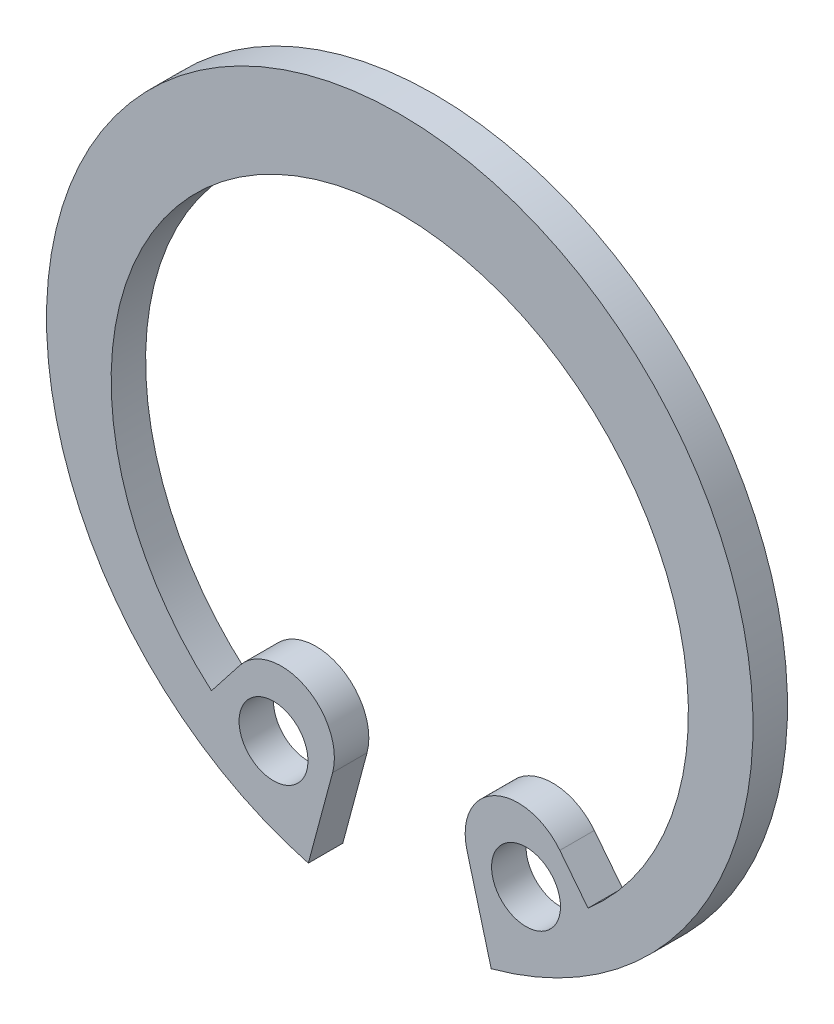
SolidWorks part; units mm, degrees
material "Steel AISI 4130 , normalized at 870°C"
ref_plane "Front" through (0, 0, 0) normal (0, 0, 1) x (1, 0, 0)
ref_plane "Top" through (0, 0, 0) normal (0, 1, 0) x (1, 0, 0)
ref_plane "Right" through (0, 0, 0) normal (1, 0, 0) x (0, 0, -1)
sketch "Layout" plane through (0, 0, 0) normal (0, 0, 1) x (1, 0, 0)
  line L0 (0, 0) -> (2.6529, -9.9007) construction
  line L1 (0, 0) -> (0, -2.175) construction
  line L2 (0, 0) -> (6.3209, -8.069) construction
  line L3 (0, 10.25) -> (0, 9) construction
  line L4 (0, -10.25) -> (0, -9) construction
  line L5 (0, 9) -> (0, 7.75) construction
  line L6 (2.7477, -5.5021) -> (0, 0) construction
  line L7 (2.7477, -5.5021) -> (4.5794, -9.1701) construction
  line L8 (-10.25, 0) -> (-9.25, 0) construction
  line L9 (1.6246, -6.0629) -> (1.974, -7.3671) construction
  line L10 (1.974, -7.3671) -> (2.3235, -8.6713) construction
  line L11 (6.3209, -8.069) -> (2.6529, -9.9007) construction
  line L12 (1.6246, -6.0629) -> (3.8708, -4.9412) construction
  circle A0 centre (0, 0) radius 10.25 construction
  circle A1 centre (0, -0.625) radius 8.375 construction
  circle A3 centre (3.6636, -7.3361) radius 1 construction
  dimension "D1" = 15
sketch "Sketch2" plane through (0, 0, 0) normal (0, 0, 1) x (1, 0, 0)
  line L0 (0, 0) -> (6.3209, -8.069) construction
  line L1 (0, 0) -> (2.6529, -9.9007) construction
  line L2 (3.8708, -4.9412) -> (5.4626, -6.9733)
  line L3 (1.6246, -6.0629) -> (2.6529, -9.9007)
  line L4 (0, 0) -> (0, -2.175) construction
  line L5 (0, 7.7639) -> (0, -6.0981) construction
  line L6 (0, 10.25) -> (0, 7.75)
  line L7 (1.6246, -6.0629) -> (3.8708, -4.9412) construction
  line L8 (1.6246, -6.0629) -> (3.8708, -4.9412)
  circle A0 centre (0, -0.625) radius 8.375 construction
  arc A1 (5.4626, -6.9733) -> (0, 7.75) centre (0, -0.625) ccw
  circle A2 centre (0, 0) radius 10.25 construction
  circle A3 centre (3.6636, -7.3361) radius 1 construction
  arc A4 (2.6529, -9.9007) -> (0, 10.25) centre (0, 0) ccw
  circle A7 centre (3.6636, -7.3361) radius 1
extrude "Boss-Extrude1" add sketch "Sketch2" along normal blind 1
fillet "Fillet1" 2 edges at (3.8708, -4.9412, 0.5) (1.6246, -6.0629, 0.5) type full round first side face at (4.6667, -5.9572, 0.5) second side face at (2.1387, -7.9818, 0.5) middle face at (2.7477, -5.5021, 0.5)
mirror "Mirror1" about plane through (0, 10.25, 1) normal (1, 0, 0) of bodies 109
equation "\"D1@Boss-Extrude1\"=\"thickness@Layout\""
